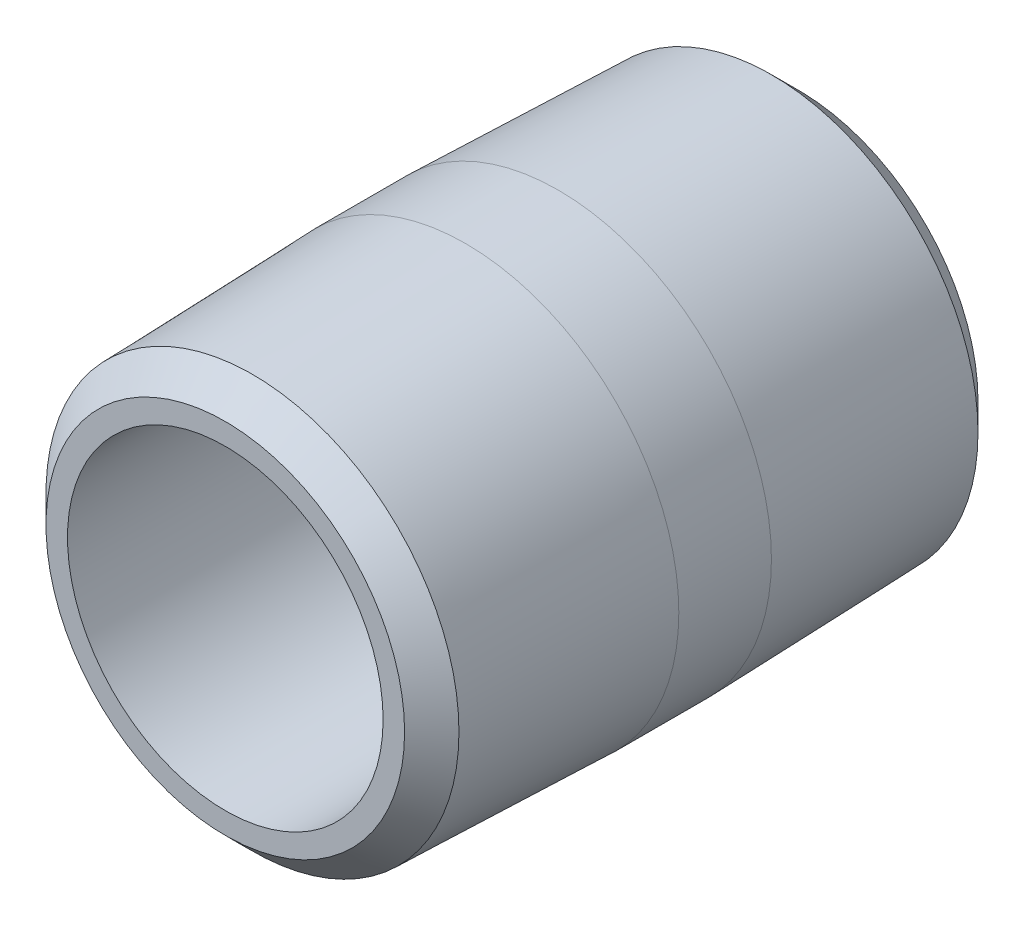
SolidWorks part; units mm, degrees
ref_plane "Front" through (0, 0, 0) normal (0, 0, 1) x (1, 0, 0)
ref_plane "Top" through (0, 0, 0) normal (0, 1, 0) x (1, 0, 0)
ref_plane "Right" through (0, 0, 0) normal (1, 0, 0) x (0, 0, -1)
sketch "Sketch1" plane through (0, 0, 0) normal (1, 0, 0) x (0, 0, -1)
  line L0 (-14.351, 0) -> (14.351, 0) construction
  line L1 (-14.351, 7.8994) -> (-14.351, 8.975)
  line L2 (-12.9903, 10.3357) -> (-2.3177, 10.668)
  line L3 (-2.3177, 10.668) -> (2.3177, 10.668)
  line L4 (-2.3177, 10.668) -> (-14.351, 10.668) construction
  line L5 (-14.351, 10.668) -> (-14.351, 8.975) construction
  line L6 (-12.9903, 10.3357) -> (-14.351, 8.975)
  line L7 (-14.351, 8.975) -> (-12.9903, 8.975) construction
  line L8 (-12.9903, 8.975) -> (-12.9903, 10.3357) construction
  line L9 (-12.9903, 10.3357) -> (-14.351, 10.2933) construction
  line L10 (-14.351, 10.2933) -> (-15.0314, 9.1149) construction
  line L11 (-15.0314, 9.1149) -> (-15.2581, 9.1149) construction
  line L12 (-15.2581, 9.1149) -> (-16.2331, 10.8036) construction
  line L13 (-16.2331, 10.8036) -> (-14.0564, 10.8036) construction
  line L14 (-14.0564, 10.8036) -> (-14.351, 10.2933) construction
  line L15 (-14.6912, 9.7041) -> (-15.5983, 9.7041) construction
  line L16 (-15.1447, 9.7041) -> (-15.1447, 9.1149) construction
  line L17 (-15.1447, 9.4095) -> (-16.959, 9.4095) construction
  line L18 (-14.351, 7.8994) -> (14.351, 7.8994)
  line L19 (0, 0) -> (0, 10.668) construction
  line L20 (14.351, 7.8994) -> (14.351, 8.975)
  line L21 (12.9903, 10.3357) -> (14.351, 8.975)
  line L22 (12.9903, 10.3357) -> (2.3177, 10.668)
  line L23 (12.9903, -10.3357) -> (2.3177, -10.668) construction
  line L24 (-2.3177, -10.668) -> (2.3177, -10.668) construction
  line L25 (-12.9903, -10.3357) -> (-2.3177, -10.668) construction
  line L26 (-4.3724, -10.604) -> (-4.3724, 0) construction
  line L27 (4.3724, -10.604) -> (4.3724, 0) construction
  point P27 (0, 7.8994)
  dimension "D1" = 1.783
  dimension "D2" = 1.3607
  dimension "D3" = 0.2268
  dimension "D4" = 0.9071
  dimension "D5" = 60
  dimension "D6" = 9.9786
revolve "Revolve1" add sketch "Sketch1" angle 360 about L0
sketch "Sketch2" plane through (0, 0, 0) normal (0, 0, 1) x (1, 0, 0)
  line L0 (-10.668, 0) -> (-7.8994, 0) construction
  line L1 (-7.8994, 0) -> (7.8994, 0) construction
  line L2 (7.8994, 0) -> (10.668, 0) construction
  circle A0 centre (0, 0) radius 7.8994 construction
  circle A1 centre (0, 0) radius 10.668 construction
  circle A2 centre (0, 0) radius 7.8994 construction
  circle A3 centre (0, 0) radius 10.668 construction
sketch "Sketch3" plane through (0, 0, 14.351) normal (0, 0, 1) x (1, 0, 0)
  circle A0 centre (0, 0) radius 10.2933
curve "Helix/Spiral1"
sketch "Sketch4" [suppressed] plane through (0, 0, 0) normal (1, 0, 0) x (0, 0, -1)
  line L0 (-16.2331, 10.8036) -> (-15.2581, 9.1149)
  line L1 (-15.2581, 9.1149) -> (-15.0314, 9.1149)
  line L2 (-15.0314, 9.1149) -> (-14.0564, 10.8036)
  line L3 (-14.0564, 10.8036) -> (-16.2331, 10.8036)
sweep "Sweep1" [suppressed] add profiles "Sketch4" path "Helix/Spiral1"
sketch "Sketch5" [suppressed] plane through (0, 0, 0) normal (1, 0, 0) x (0, 0, -1)
  line L0 (-14.351, 0) -> (14.351, 0) construction
  line L1 (14.351, -8.8537) -> (-2.3177, -8.8537)
  line L2 (14.351, -8.8537) -> (14.351, 8.8537)
  line L3 (14.351, 8.8537) -> (-2.3177, 8.8537)
  line L4 (-2.3177, -8.8537) -> (-2.3177, 8.8537)
  line L5 (14.351, -8.8537) -> (-2.3177, 8.8537) construction
  line L6 (14.351, 8.8537) -> (-2.3177, -8.8537) construction
  line L7 (-2.3177, 10.668) -> (2.3177, 10.668) construction
  line L8 (14.351, -8.975) -> (14.351, 8.975) construction
  point P0 (6.0166, 0)
  dimension "D1" = 1.8143
extrude "Cut-Extrude1" [suppressed] cut sketch "Sketch5" against normal through all both and the other way through all
ref_axis "Axis1" [suppressed] through (0, 0, 0) along (0, 1, 0)
pattern_circular "CirPattern1" [suppressed] count 2 over 180 about axis through (0, 0, 0) along (0, 1, 0) of bodies 111
combine bodies "Combine1" [suppressed] operation type add bodies to combine 109 111 112
sketch "Sketch6" [suppressed] plane through (0, 0, 0) normal (1, 0, 0) x (0, 0, -1)
  line L0 (-2.3177, 10.668) -> (-10.482, 7.8994)
  line L1 (-14.351, 7.8994) -> (14.351, 7.8994) construction
  line L2 (-10.482, 7.8994) -> (10.482, 7.8994)
  line L3 (-2.3177, 10.668) -> (2.3177, 10.668)
  line L4 (-2.3177, 10.668) -> (2.3177, 10.668) construction
  line L5 (0, 10.668) -> (0, 7.8994) construction
  line L6 (2.3177, 10.668) -> (10.482, 7.8994)
  line L7 (-14.351, 0) -> (14.351, 0) construction
  dimension "D1" = 8.1643
revolve "Revolve2" [suppressed] add sketch "Sketch6" angle 360 about L7
equation "\"D3@Sketch1\"=\"Pitch@Sketch1\"*.125"
equation "\"D4@Sketch1\"=\"Pitch@Sketch1\"*.5"
equation "\"D2@Sketch1\"=\"Pitch@Sketch1\"*.75"
equation "\"D4@Helix/Spiral1\"=\"Pitch@Sketch1\""
equation "\"D3@Helix/Spiral1\"=\"ThreadLength@Sketch1\"+\"Pitch@Sketch1\""
equation "\"D1@Sketch5\"=\"Pitch@Sketch1\""
equation "\"D1@Sketch6\"=\"Pitch@Sketch1\"*4.5"
equation "\"D6@Sketch1\"=\"Pitch@Sketch1\"*5.5"
equation "\"ThreadLength@Sketch1\"=0.59375000-.12"
